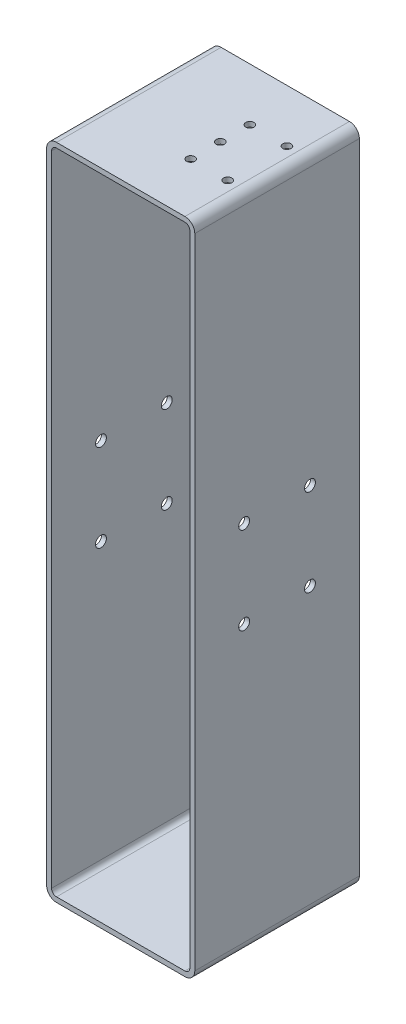
SolidWorks part; units mm, degrees
ref_plane "Front Plane" through (0, 0, 0) normal (0, 0, 1) x (1, 0, 0)
ref_plane "Top Plane" through (0, 0, 0) normal (0, 1, 0) x (1, 0, 0)
ref_plane "Right Plane" through (0, 0, 0) normal (1, 0, 0) x (0, 0, -1)
sketch "Sketch1" plane through (0, 0, 0) normal (0, 0, 1) x (1, 0, 0)
  line L0 (39, 197) -> (-39, 197)
  line L1 (39, -200) -> (-39, -200)
  line L2 (45, -194) -> (45, 194)
  line L3 (39, 200) -> (-39, 200)
  line L4 (-45, -194) -> (-45, 194)
  line L5 (45, -200) -> (-45, 200) construction
  line L6 (45, 200) -> (-45, -200) construction
  line L7 (-42, -194) -> (-42, 194)
  line L8 (39, -197) -> (-39, -197)
  line L9 (42, -194) -> (42, 194)
  arc A0 (-39, -200) -> (-45, -194) centre (-39, -194) cw
  arc A1 (39, -200) -> (45, -194) centre (39, -194) ccw
  arc A2 (45, 194) -> (39, 200) centre (39, 194) ccw
  arc A3 (-39, 200) -> (-45, 194) centre (-39, 194) ccw
  arc A4 (-39, 197) -> (-42, 194) centre (-39, 194) ccw
  arc A5 (-39, -197) -> (-42, -194) centre (-39, -194) cw
  arc A6 (39, -197) -> (42, -194) centre (39, -194) ccw
  arc A7 (42, 194) -> (39, 197) centre (39, 194) ccw
  point P0 (0, 0)
  dimension "D1" = 6
  dimension "D3" = 400
  dimension "D4" = 90
  dimension "D2" = 3
extrude "Boss-Extrude1" add sketch "Sketch1" along normal mid plane 100
sketch "Sketch2" plane through (45, 0, 0) normal (1, 0, 0) x (0, 0, -1)
  line L1 (20, 26.5) -> (-20, 26.5) construction
  line L2 (20, 26.5) -> (20, -26.5) construction
  line L3 (20, -26.5) -> (-20, -26.5) construction
  line L4 (-20, 26.5) -> (-20, -26.5) construction
  line L5 (20, 26.5) -> (-20, -26.5) construction
  line L6 (20, -26.5) -> (-20, 26.5) construction
  circle A0 centre (-20, 26.5) radius 3.3
  circle A1 centre (20, 26.5) radius 3.3
  circle A2 centre (20, -26.5) radius 3.3
  circle A3 centre (-20, -26.5) radius 3.3
  point P0 (0, 0)
  dimension "D3" = 6.6
  dimension "D1" = 53
  dimension "D2" = 40
extrude "Cut-Extrude1" cut sketch "Sketch2" against normal through all
sketch "Sketch3" plane through (0, 200, 0) normal (0, 1, 0) x (1, 0, 0)
  line L0 (-24.6642, 0) -> (5.453, 0) construction
  line L1 (10.5, 18) -> (10.5, -18) construction
  line L2 (10.5, 18) -> (33, 18) construction
  line L3 (33, 18) -> (33, -18) construction
  line L4 (45, -50) -> (45, 50) construction
  circle A0 centre (10.5, 18) radius 2.5
  circle A1 centre (10.5, 0) radius 2.5
  circle A2 centre (10.5, -18) radius 2.5
  circle A3 centre (33, 18) radius 2.5
  circle A4 centre (33, -18) radius 2.5
  point P5 (10.5, 0)
  dimension "D2" = 5
  dimension "D1" = 36
  dimension "D3" = 22.5
  dimension "D4" = 12
extrude "Cut-Extrude2" cut sketch "Sketch3" against normal up to surface (3 mm away) up to face at (0, 197, 0)
equation "\"M5_tap\"=4.2mm"
equation "\"M5_clearence\"=5.5mm"
equation "\"M6_tap\"=5mm"
equation "\"M6_clearence\"=6.6mm"
equation "\"work_area_width\"=1100mm"
equation "\"work_area_depth\"=900mm"
equation "\"D3@Sketch1\"=\"steel_zbox_width\""
equation "\"D4@Sketch1\"=\"steel_zbox_height\""
equation "\"D1@Sketch1\"=\"steel_zbox_radius\""
equation "\"D2@Sketch1\"=\"steel_zbox_wall_thickness\""
equation "\"D1@Boss-Extrude1\"=\"length\""
equation "\"steel_base_width\"=80mm"
equation "\"steel_base_height\"=50mm"
equation "\"steel_base_wall_thickness\"=3mm"
equation "\"steel_base_radius\"=6mm"
equation "\"steel_sides_width\"=180mm"
equation "\"steel_sides_height\"=50mm"
equation "\"steel_sides_wall_thickness\"=5mm"
equation "\"steel_sides_radius\"=6mm"
equation "\"steel_gantry_width\"=120mm"
equation "\"steel_gantry_height\"=80mm"
equation "\"steel_gantry_wall_thickness\"=6mm"
equation "\"steel_gantry_radius\"=6mm"
equation "\"D3@Sketch2\"=\"M6_clearence\""
equation "\"D2@Sketch3\"=\"M6_tap\""
equation "\"steel_rollers_width\"=80mm"
equation "\"steel_rollers_height\"=50mm"
equation "\"steel_rollers_wall_thickness\"=6mm"
equation "\"steel_rollers_radius\"=6mm"
equation "\"steel_zbox_width\"=400mm"
equation "\"steel_zbox_height\"=90mm"
equation "\"steel_zbox_wall_thickness\"=3mm"
equation "\"steel_zbox_radius\"=6mm"
equation "\"D4@Sketch3\"=\"steel_zbox_radius\" * 2"
equation "\"length\"= 100mm"
